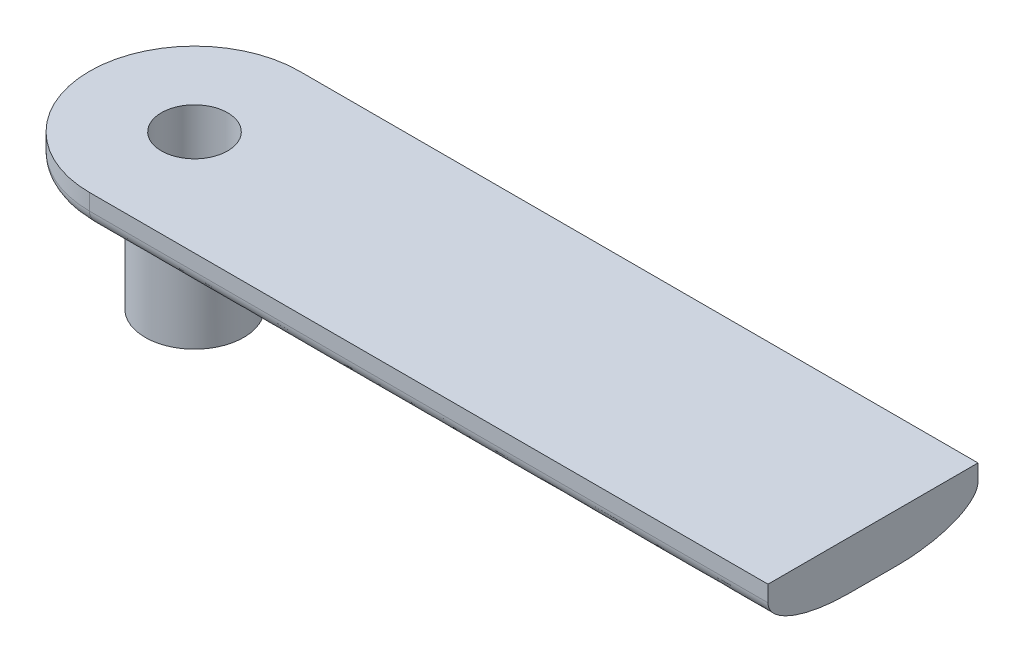
SolidWorks part; units mm, degrees
ref_plane "Front Plane" through (0, 0, 0) normal (0, 0, 1) x (1, 0, 0)
ref_plane "Top Plane" through (0, 0, 0) normal (0, 1, 0) x (1, 0, 0)
ref_plane "Right Plane" through (0, 0, 0) normal (1, 0, 0) x (0, 0, -1)
sketch "Sketch1" plane through (0, 0, 0) normal (0, 1, 0) x (1, 0, 0)
  line L1 (0, 6.5) -> (42, 6.5)
  line L2 (0, 6.5) -> (0, -6.5) construction
  line L3 (0, -6.5) -> (42, -6.5)
  line L4 (42, 6.5) -> (42, -6.5)
  arc A0 (0, 6.5) -> (0, -6.5) centre (0, 0) ccw
  arc A1 (0, -6.5) -> (0, 6.5) centre (0, 0) ccw construction
  dimension "D1" = 13
  dimension "D2" = 42
extrude "Boss-Extrude1" add sketch "Sketch1" along normal blind 3
fillet "Fillet1" radius 5 3 edges at (21, 0, -6.5) (-6.5, 0, 0) (21, 0, 6.5) second distance 2 first distance on face at (19.375, 0, 0)
sketch "Sketch2" plane through (0, 3, 0) normal (0, 1, 0) x (1, 0, 0)
  circle A0 centre (0, 0) radius 2.05
  circle A2 centre (0, 0) radius 3.05
  dimension "D1" = 4.1
  dimension "D2" = 1
extrude "Boss-Extrude3" add sketch "Sketch2" along a picked direction on the side against the normal offset from surface (9.5 mm away) 6.5 contours A2 A0
sketch "Sketch3" plane through (0, 3, 0) normal (0, 1, 0) x (1, 0, 0)
  circle A1 centre (0, 0) radius 2.05
  circle A2 centre (0, 0) radius 2.05 construction
extrude "Cut-Extrude1" cut sketch "Sketch3" against normal through all
